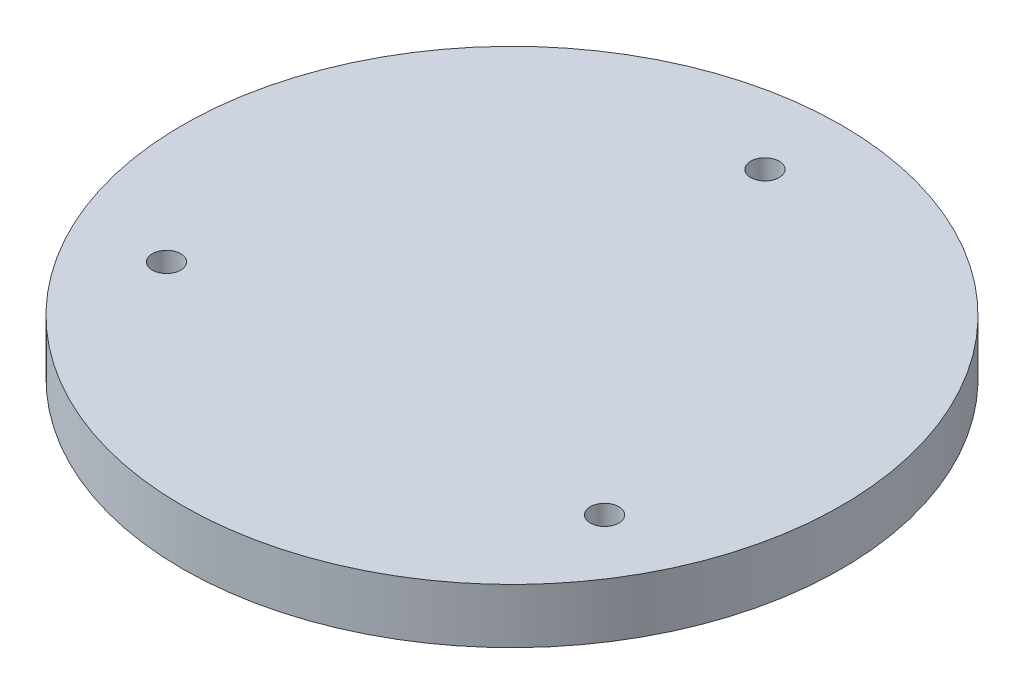
SolidWorks part; units mm, degrees
material "G10 Fiberglass"
ref_plane "Front Plane" through (0, 0, 0) normal (0, 0, 1) x (1, 0, 0)
ref_plane "Top Plane" through (0, 0, 0) normal (0, 1, 0) x (1, 0, 0)
ref_plane "Right Plane" through (0, 0, 0) normal (1, 0, 0) x (0, 0, -1)
sketch "Sketch1" plane through (0, 0, 0) normal (0, 1, 0) x (1, 0, 0)
  circle A0 centre (0, 0) radius 38.227
  dimension "D1" = 76.454
extrude "Boss-Extrude1" add sketch "Sketch1" along normal blind 6.35
ref_axis "Axis1" through (0, 6.6675, 0) along (0, -1, 0)
sketch "Sketch2" plane through (0, 6.35, 0) normal (0, 1, 0) x (1, 0, 0)
  circle A0 centre (0, 29.337) radius 1.651
  circle A1 centre (25.4066, -14.6685) radius 1.651
  circle A2 centre (-25.4066, -14.6685) radius 1.651
  point P10 (0, 0)
  dimension "D1" = 3.302
  dimension "D3" = 29.337
  dimension "D2" = 3
extrude "Cut-Extrude1" cut sketch "Sketch2" against normal through all
equation "\"D5@Sketch2\"=\"D4@Sketch2\""
